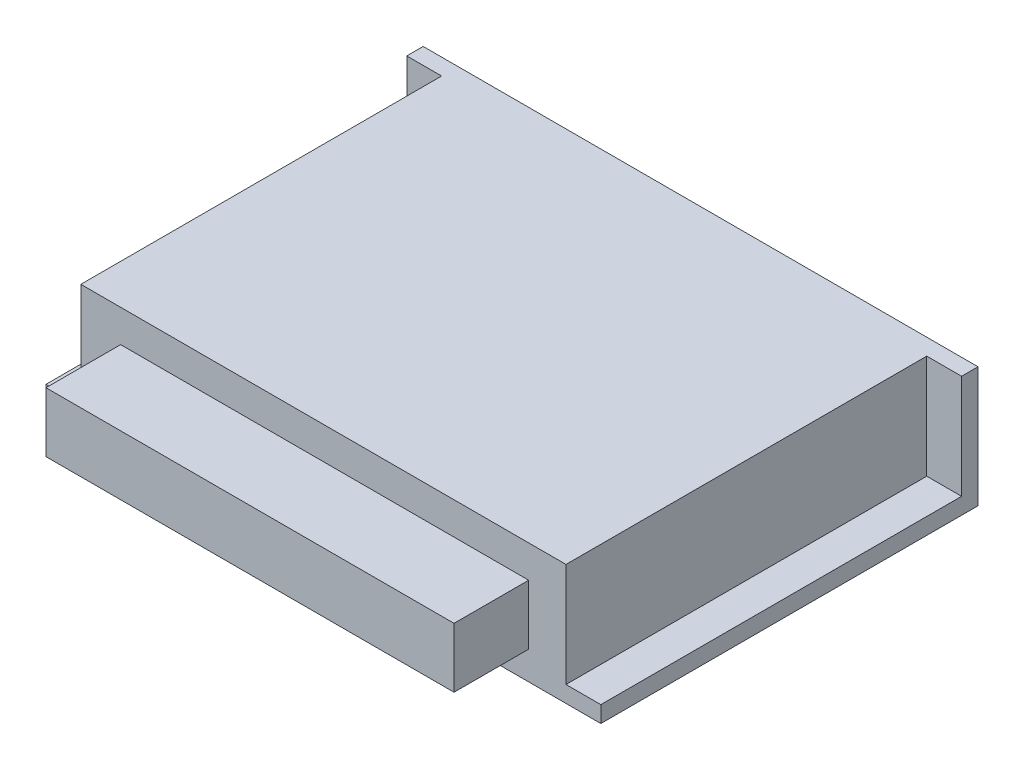
SolidWorks part; units mm, degrees
ref_plane "Front" through (0, 0, 0) normal (0, 0, 1) x (1, 0, 0)
ref_plane "Top" through (0, 0, 0) normal (0, 1, 0) x (1, 0, 0)
ref_plane "Right" through (0, 0, 0) normal (1, 0, 0) x (0, 0, -1)
sketch "Sketch1" plane through (0, 0, 0) normal (0, 1, 0) x (1, 0, 0)
  line L1 (-55.75, -37.9) -> (55.75, -37.9)
  line L2 (-55.75, -37.9) -> (-55.75, 37.9)
  line L3 (-55.75, 37.9) -> (55.75, 37.9)
  line L4 (55.75, -37.9) -> (55.75, 37.9)
  line L5 (-55.75, -37.9) -> (55.75, 37.9) construction
  line L6 (-55.75, 37.9) -> (55.75, -37.9) construction
  point P0 (0, 0)
  dimension "D1" = 111.5
  dimension "D2" = 75.8
extrude "Boss-Extrude1" add sketch "Sketch1" along normal blind 3.3
sketch "Sketch2" plane through (0, 3.3, 0) normal (0, 1, 0) x (1, 0, 0)
  line L0 (55.75, 37.9) -> (-55.75, 37.9) construction
  line L1 (-48.75, 37.9) -> (48.75, 37.9)
  line L2 (-48.75, 34.6) -> (-48.75, -37.9)
  line L3 (-48.75, -37.9) -> (48.75, -37.9)
  line L4 (48.75, 34.6) -> (48.75, -37.9)
  line L5 (-55.75, 37.9) -> (-55.75, -37.9) construction
  line L6 (-55.75, -37.9) -> (55.75, -37.9) construction
  line L7 (55.75, -37.9) -> (55.75, 37.9) construction
  line L8 (-55.75, 37.9) -> (55.75, 37.9)
  line L9 (-55.75, 37.9) -> (-55.75, 34.6)
  line L10 (-55.75, 34.6) -> (-48.75, 34.6)
  line L11 (55.75, 37.9) -> (55.75, 34.6)
  line L12 (48.75, 34.6) -> (55.75, 34.6)
  point P6 (0, -37.9)
  line M10 (55.75, -37.9) -> (55.75, 37.9)
  line M11 (55.75, 37.9) -> (-55.75, 37.9)
  line M12 (-55.75, 37.9) -> (-55.75, -37.9)
  line M13 (-55.75, -37.9) -> (55.75, -37.9)
  dimension "D1" = 7
  dimension "D2" = 3.3
extrude "Boss-Extrude2" add sketch "Sketch2" along normal offset from surface (20.9 mm away) 24.2 contours L4 L12 L10 L2 M10 M11 M12 M13 region at (0, 3.3, -0.2252) up to face at (0, 0, 0)
sketch "Sketch3" plane through (0, 0, 37.9) normal (0, 0, 1) x (1, 0, 0)
  line L1 (-40.75, 5.7) -> (41.25, 5.7)
  line L2 (-40.75, 5.7) -> (-40.75, 17.7)
  line L3 (-40.75, 17.7) -> (41.25, 17.7)
  line L4 (41.25, 5.7) -> (41.25, 17.7)
  line L5 (-48.75, 24.2) -> (-48.75, 3.3) construction
  line L6 (48.75, 24.2) -> (-48.75, 24.2) construction
  dimension "D1" = 82
  dimension "D2" = 8
  dimension "D3" = 6.5
  dimension "D4" = 12
extrude "Boss-Extrude3" add sketch "Sketch3" along normal blind 15
